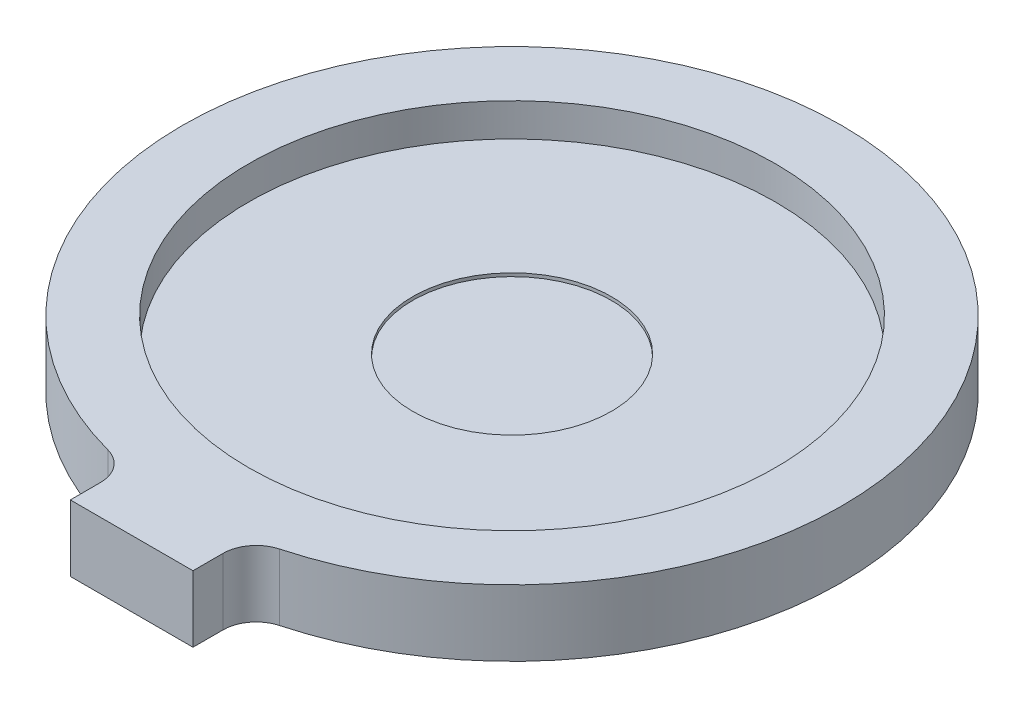
SolidWorks part; units mm, degrees
material "Alloy Steel"
ref_plane "Front" through (0, 0, 0) normal (0, 0, 1) x (1, 0, 0)
ref_plane "Top" through (0, 0, 0) normal (0, 1, 0) x (1, 0, 0)
ref_plane "Right" through (0, 0, 0) normal (1, 0, 0) x (0, 0, -1)
sketch "Sketch1" plane through (0, 0, 0) normal (0, 1, 0) x (1, 0, 0)
  circle A0 centre (0, 0) radius 9945.75
  dimension "D1" = 19891.5
extrude "Boss-Extrude1" add sketch "Sketch1" along normal blind 2000
sketch "Sketch2" plane through (0, 2000, 0) normal (0, 1, 0) x (1, 0, 0)
  circle A0 centre (0, 0) radius 7945.75
  circle A1 centre (0, 0) radius 9945.75 construction
  dimension "D1" = 2000
extrude "Cut-Extrude1" cut sketch "Sketch2" against normal blind 1000
sketch "Sketch3" plane through (0, 1000, 0) normal (0, 1, 0) x (1, 0, 0)
  circle A0 centre (0, 0) radius 3000
  dimension "D1" = 6000
extrude "Cut-Extrude2" cut sketch "Sketch3" against normal blind 100
sketch "Sketch4" plane through (0, 0, 0) normal (0, -1, 0) x (1, 0, 0)
  line L0 (0, 6860.9215) -> (0, 13231.5292) construction
  line L1 (-1850, 9475.9937) -> (1850, 9475.9937)
  line L2 (-1850, 9475.9937) -> (-1850, 11475.9937)
  line L3 (-1850, 11475.9937) -> (1850, 11475.9937)
  line L4 (1850, 9475.9937) -> (1850, 11475.9937)
  dimension "D1" = 3700
  dimension "D2" = 1850
  dimension "D3" = 2000
extrude "Boss-Extrude2" add sketch "Sketch4" against normal up to surface (2000 mm away) up to face at (0, 2000, 7945.75)
fillet "Fillet1" radius 1000 2 edges at (-1850, 1000, 9772.177) (1850, 1000, 9772.177)
equation "\"Radius\"= 12"
equation "\"diameter\"=19.8915"
equation "\"D1@Sketch1\"=\"diameter\""
equation "\"height\"= 2"
equation "\"D1@Boss-Extrude1\"=\"height\""
equation "\"pit\"=2"
equation "\"D1@Sketch2\"=\"pit\""
equation "\"basehole\"=6"
equation "\"D1@Sketch3\"=\"basehole\""
